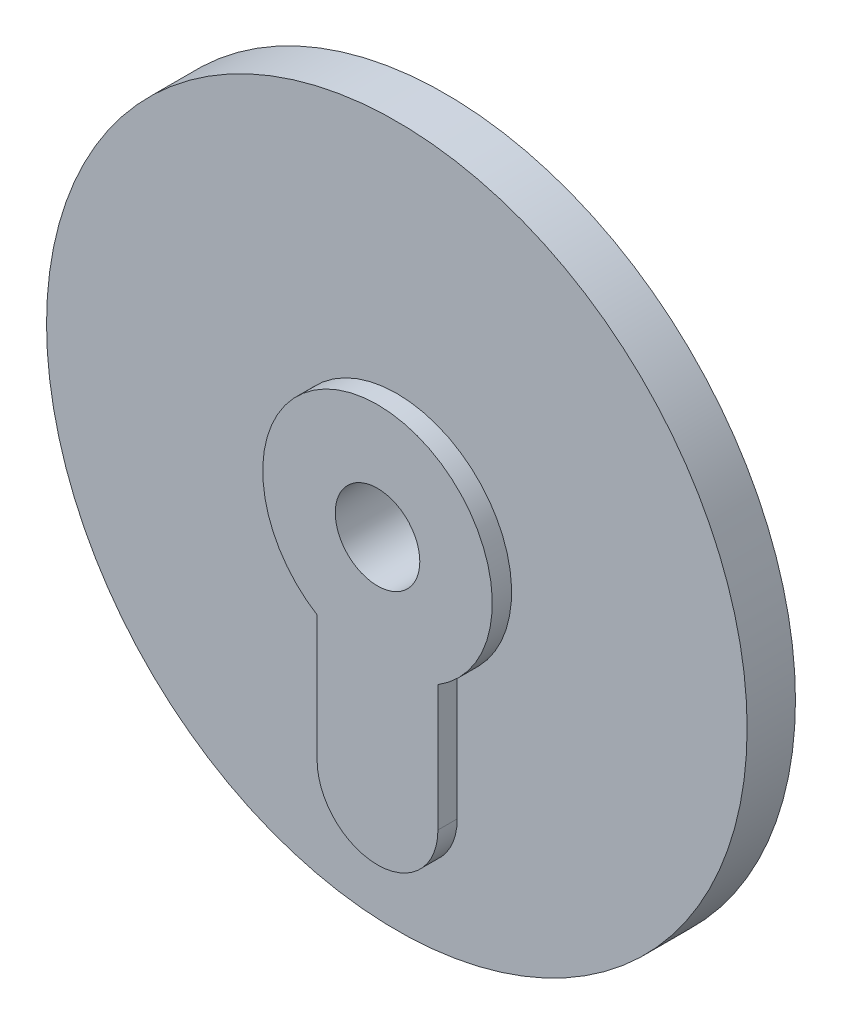
SolidWorks part; units mm, degrees
ref_plane "Спереди" through (0, 0, 0) normal (0, 0, 1) x (1, 0, 0)
ref_plane "Сверху" through (0, 0, 0) normal (0, 1, 0) x (1, 0, 0)
ref_plane "Справа" through (0, 0, 0) normal (1, 0, 0) x (0, 0, -1)
sketch "Эскиз1" plane through (0, 0, 0) normal (0, 0, 1) x (1, 0, 0)
  line L0 (-2.5, -4.0389) -> (-2.5, -9.25)
  line L1 (2.5, -4.0389) -> (2.5, -9.25)
  line L2 (0, 8.1134) -> (0, -19.5457) construction
  line L3 (-9.7984, 4.75) -> (17.7492, 4.75) construction
  line L4 (-12.252, -11.75) -> (16.0763, -11.75) construction
  arc A0 (-2.5, -4.0389) -> (2.5, -4.0389) centre (0, 0) cw
  arc A1 (2.5, -9.25) -> (-2.5, -9.25) centre (0, -9.25) cw
  circle A2 centre (0, 0) radius 14.5
  circle A3 centre (0, 0) radius 1.75
  dimension "D1" = 2.5
  dimension "D2" = 4.75
  dimension "D4" = 29
  dimension "D5" = 3.5
  dimension "D3" = 16.5
extrude "Бобышка-Вытянуть1" add sketch "Эскиз1" along normal blind 2 contours A2
extrude "Бобышка-Вытянуть2" add sketch "Эскиз1<3>" along normal blind 0.8 from surface contours L1 A1 L0 A0 starting at face at (14.5, 0, 2)
sketch "Эскиз1<3>" plane through (0, 0, 0) normal (0, 0, 1) x (1, 0, 0) same geometry as "Эскиз1"
extrude "Вырез-Вытянуть1" cut sketch "Эскиз1<4>" along normal blind 2.8 contours A3
sketch "Эскиз1<4>" plane through (0, 0, 0) normal (0, 0, 1) x (1, 0, 0) same geometry as "Эскиз1"
